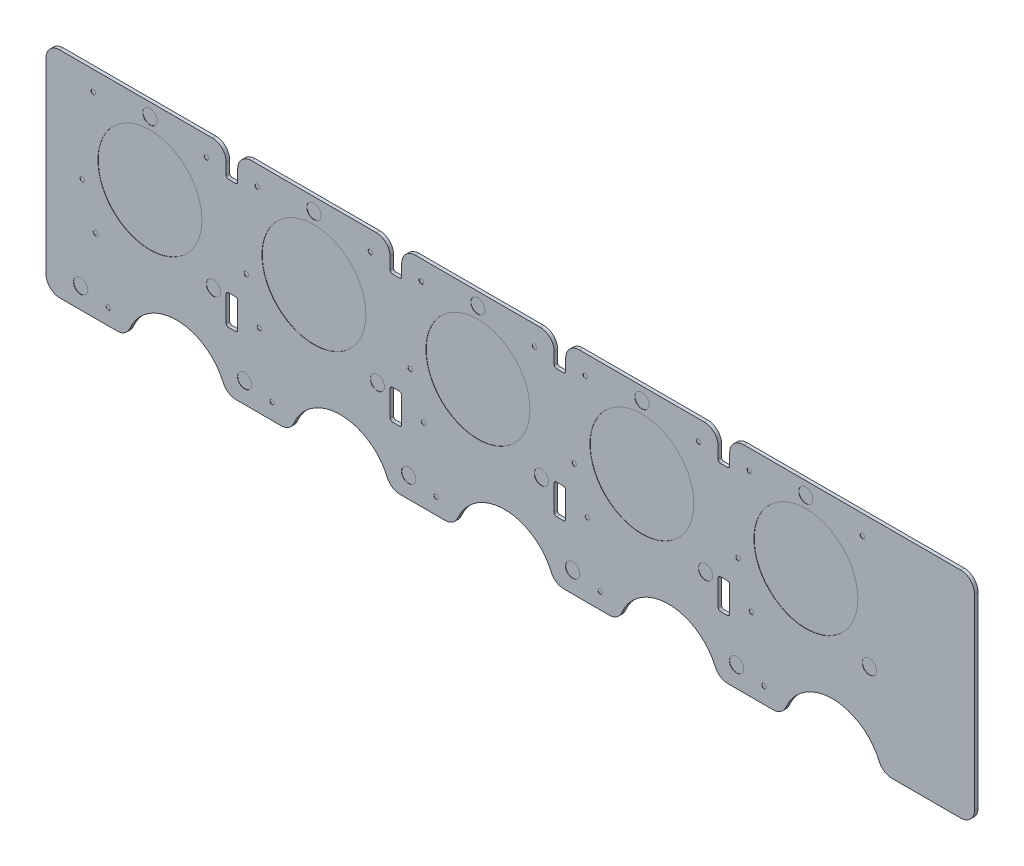
SolidWorks part; units mm, degrees
ref_plane "Plan de face" through (0, 0, 0) normal (0, 0, 1) x (1, 0, 0)
ref_plane "Plan de dessus" through (0, 0, 0) normal (0, 1, 0) x (1, 0, 0)
ref_plane "Plan de droite" through (0, 0, 0) normal (1, 0, 0) x (0, 0, -1)
sketch "Esquisse1" plane through (0, 0, 0) normal (0, 0, 1) x (1, 0, 0)
  line L0 (-142, 0) -> (-71, 0) construction
  line L1 (-187, 33) -> (215, 33)
  line L2 (-187, 33) -> (-187, -60)
  line L3 (-187, -60) -> (215, -60)
  line L4 (215, 33) -> (215, -60)
  line L5 (-71, 0) -> (0, 0) construction
  line L6 (0, 0) -> (71, 0) construction
  line L7 (71, 0) -> (142, 0) construction
  line L8 (-142, 0) -> (-187, 0) construction
  line L9 (142, 0) -> (215, 0) construction
  circle A0 centre (-142, 0) radius 22.5
  circle A1 centre (-71, 0) radius 22.5
  circle A2 centre (0, 0) radius 22.5
  circle A3 centre (71, 0) radius 22.5
  circle A4 centre (142, 0) radius 22.5
  dimension "D1" = 71
  dimension "D2" = 45
  dimension "D3" = 45
  dimension "D4" = 33
  dimension "D5" = 60
  dimension "D6" = 73
  dimension "D7" = 402
extrude "PCB_rectangulaire" add sketch "Esquisse1" against normal blind 1.5 contours L1 L4 L3 L2
extrude "position_trou" cut sketch "Esquisse1<3>" against normal blind 0.1 contours A0 | A1 | A2 | A3 | A4 region at (-142, 0, 0) region at (-71, 0, 0) region at (0, 0, 0) region at (71, 0, 0)
sketch "Esquisse1<3>" plane through (0, 0, 0) normal (0, 0, 1) x (1, 0, 0) same geometry as "Esquisse1"
sketch "Esquisse3" plane through (0, 0, 0) normal (0, 0, 1) x (1, 0, 0)
  line L0 (-187, 33) -> (215, 33) construction
  line L1 (-109, 33) -> (-104, 33)
  line L2 (-109, 33) -> (-109, 22)
  line L3 (-108, 21) -> (-105, 21)
  line L4 (-104, 33) -> (-104, 22)
  line L5 (-106.5, 21) -> (-106.5, 0) construction
  line L6 (-108, -21.5) -> (-105, -21.5)
  line L7 (-109, -22.5) -> (-109, -33.5)
  line L8 (-108, -34.5) -> (-105, -34.5)
  line L9 (-104, -22.5) -> (-104, -33.5)
  line L10 (-106.5, 0) -> (-106.5, -21.5) construction
  line L11 (-142, 0) -> (-71, 0) construction
  arc A0 (-105, 21) -> (-104, 22) centre (-105, 22) ccw
  arc A1 (-109, 22) -> (-108, 21) centre (-108, 22) ccw
  arc A2 (-105, -34.5) -> (-104, -33.5) centre (-105, -33.5) ccw
  arc A3 (-109, -33.5) -> (-108, -34.5) centre (-108, -33.5) ccw
  arc A4 (-105, -21.5) -> (-104, -22.5) centre (-105, -22.5) cw
  arc A5 (-108, -21.5) -> (-109, -22.5) centre (-108, -22.5) ccw
  point P17 (-104, -28)
  point P20 (-104, 21)
  point P25 (-104, -34.5)
  point P28 (-109, -34.5)
  point P31 (-104, -21.5)
  point P36 (-135.3993, -74.2444)
  dimension "D5" = 1
  dimension "D1" = 5
  dimension "D2" = 12
  dimension "D3" = 13
  dimension "D4" = 28
extrude "passage_appui_flanc et passage jeton" cut sketch "Esquisse3" against normal through all
pattern_linear "Répétition linéaire1" count 4 spacing 71 along (1, 0, 0) of "passage_appui_flanc et passage jeton"
sketch "Esquisse2" plane through (0, 0, 0) normal (0, 0, 1) x (1, 0, 0)
  line L6 (-166.4921, 24.4921) -> (-164.9365, 22.9365) construction
  line L7 (-117.5079, 24.4921) -> (-119.0635, 22.9365) construction
  line L8 (-166.4921, 24.4921) -> (-117.5079, 24.4921) construction
  circle A0 centre (-171.2929, -10.7071) radius 1
  circle A1 centre (-165.5494, -28) radius 1
  circle A2 centre (-160.0562, -53.0562) radius 1
  circle A3 centre (-166.4921, 24.4921) radius 1
  circle A4 centre (-117.5079, 24.4921) radius 1
  circle A5 centre (-172, -51) radius 3.1
  circle A6 centre (-114.5, -23) radius 3.1
  circle A7 centre (-142, 27.5) radius 3.1
  point P10 (-171.2929, -10.7071)
  point P15 (-167.5799, -26.5224)
  point P16 (-160.0562, -53.0562)
  point P34 (-167.5494, -26)
  point P35 (-159.9771, -52.9771)
  dimension "D1" = 2
  dimension "D2" = 6.2
  dimension "D3" = 2.2
extrude "position_capteur-LED" cut sketch "Esquisse2" against normal blind 0.1
sketch "Esquisse4" plane through (0, 0, 0) normal (0, 0, 1) x (1, 0, 0)
  line L0 (-130.5, -65) -> (-59.5, -65) construction
  line L1 (-59.5, -65) -> (11.5, -65) construction
  line L2 (11.5, -65) -> (82.5, -65) construction
  line L3 (82.5, -65) -> (153.5, -65) construction
  line L4 (-142, 0) -> (-71, 0) construction
  circle A0 centre (-130.5, -65) radius 22
  circle A1 centre (-59.5, -65) radius 22 construction
  circle A2 centre (11.5, -65) radius 22 construction
  circle A3 centre (82.5, -65) radius 22 construction
  circle A4 centre (153.5, -65) radius 22 construction
  dimension "D1" = 44
  dimension "D2" = 11.5
  dimension "D3" = 65
extrude "echappement" cut sketch "Esquisse4" against normal through all
pattern_linear "Répétition linéaire3" count 5 spacing 71 along (1, 0, 0) of "position_capteur-LED", "echappement"
fillet "Congé1" radius 6 22 edges at (-187, -60, -0.75) (-187, 33, -0.75) (-109, 33, -0.75) (-104, 33, -0.75) (-38, 33, -0.75) (-33, 33, -0.75) (33, 33, -0.75) (38, 33, -0.75) (104, 33, -0.75) (109, 33, -0.75) (215, 33, -0.75) (215, -60, -0.75) (-109.0757, -60, -0.75) (-151.9243, -60, -0.75) (174.9243, -60, -0.75) (132.0757, -60, -0.75) (103.9243, -60, -0.75) (61.0757, -60, -0.75) (32.9243, -60, -0.75) (-9.9243, -60, -0.75) (-38.0757, -60, -0.75) (-80.9243, -60, -0.75)
